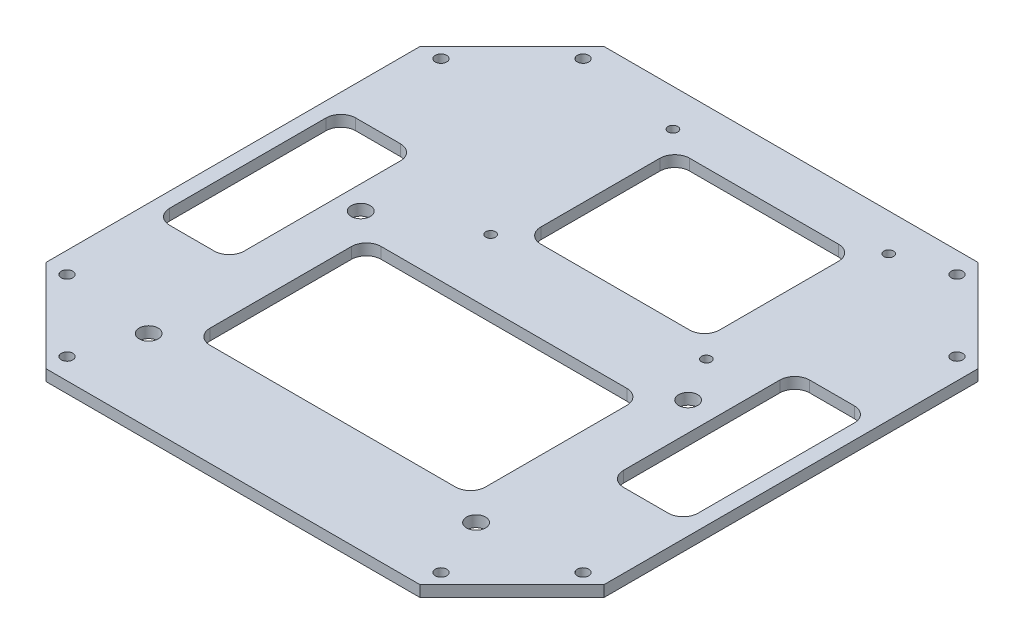
SolidWorks part; units mm, degrees
ref_plane "Front Plane" through (0, 0, 0) normal (0, 0, 1) x (1, 0, 0)
ref_plane "Top Plane" through (0, 0, 0) normal (0, 1, 0) x (1, 0, 0)
ref_plane "Right Plane" through (0, 0, 0) normal (1, 0, 0) x (0, 0, -1)
sketch "Sketch1" plane through (0, 0, 0) normal (0, 1, 0) x (1, 0, 0)
  line L1 (-75, 75) -> (75, 75)
  line L2 (-75, 75) -> (-75, -75)
  line L3 (-75, -75) -> (75, -75)
  line L4 (75, 75) -> (75, -75)
  line L5 (-75, 75) -> (75, -75) construction
  line L6 (-75, -75) -> (75, 75) construction
  point P0 (0, 0)
  dimension "D1" = 150
extrude "Boss-Extrude1" add sketch "Sketch1" along normal mid plane 3
sketch "Sketch2" plane through (0, 1.5, 0) normal (0, 1, 0) x (1, 0, 0)
  line L0 (50.2513, 75) -> (75, 75)
  line L1 (-15, 15) -> (15, 15)
  line L2 (-15, 15) -> (-15, -15)
  line L3 (-15, -15) -> (15, -15)
  line L4 (15, 15) -> (15, -15)
  line L5 (-15, 15) -> (15, -15) construction
  line L6 (-15, -15) -> (15, 15) construction
  line L7 (75, 75) -> (-75, 75) construction
  line L8 (75, -75) -> (75, 75) construction
  line L9 (75, 75) -> (75, 50.2513)
  line L10 (75, 50.2513) -> (50.2513, 75)
  line L11 (0, 0) -> (-24.6603, 0) construction
  line L12 (0, 0) -> (0, -37.7235) construction
  line L13 (-75, 75) -> (-75, 50.2513)
  line L14 (-50.2513, 75) -> (-75, 75)
  line L15 (-75, 50.2513) -> (-50.2513, 75)
  line L16 (-50.2513, -75) -> (-75, -75)
  line L17 (-75, -50.2513) -> (-50.2513, -75)
  line L18 (-75, -75) -> (-75, -50.2513)
  line L19 (75, -75) -> (75, -50.2513)
  line L20 (50.2513, -75) -> (75, -75)
  line L21 (75, -50.2513) -> (50.2513, -75)
  point P0 (0, 0)
  dimension "D1" = 30
  dimension "D2" = 35
extrude "Cut-Extrude1" cut sketch "Sketch2" against normal up to surface (3 mm away) contours L10 L0 L9 | L13 L15 L14 | L19 L21 L20 | L16 L18 L17 up to face at (0, -1.5, 0)
sketch "Sketch3" plane through (0, 1.5, 0) normal (0, 1, 0) x (1, 0, 0)
  line L0 (75, 50.2513) -> (50.2513, 75) construction
  line L1 (10, 10) -> (-10, 10)
  line L2 (10, 10) -> (10, -10)
  line L3 (10, -10) -> (-10, -10)
  line L4 (-10, 10) -> (-10, -10)
  line L5 (10, 10) -> (-10, -10) construction
  line L6 (10, -10) -> (-10, 10) construction
  line L7 (0, 0) -> (0, -7.7356) construction
  line L8 (0, 0) -> (-6.2026, 0) construction
  circle A2 centre (69.3431, 50.2513) radius 1.55
  circle A6 centre (50.2513, 69.3431) radius 1.55
  circle A7 centre (-69.3431, 50.2513) radius 1.55
  circle A12 centre (-50.2513, 69.3431) radius 1.55
  circle A14 centre (-69.3431, -50.2513) radius 1.55
  circle A18 centre (-50.2513, -69.3431) radius 1.55
  circle A19 centre (69.3431, -50.2513) radius 1.55
  circle A24 centre (50.2513, -69.3431) radius 1.55
  point P0 (0, 0)
  dimension "D2" = 13.5
  dimension "D4" = 3.1
  dimension "D8" = 4
  dimension "D1" = 20
extrude "Cut-Extrude2" cut sketch "Sketch3" against normal up to surface (3 mm away) contours A12 | A7 | A14 | A18 | A19 | A24 | A2 | A6 region at (69.3431, 1.5, -50.2513) region at (50.2513, 1.5, -69.3431) region at (-69.3431, 1.5, -50.2513) region at (-50.2513, 1.5, -69.3431) region at (-69.3431, 1.5, 50.2513) region at (-50.2513, 1.5, 69.3431) region at (69.3431, 1.5, 50.2513) region at (50.2513, 1.5, 69.3431) up to face at (0, -1.5, 0)
sketch "Sketch6" plane through (0, 1.5, 0) normal (0, 1, 0) x (1, 0, 0)
  line L0 (0, 0) -> (-24.3812, 0) construction
  line L2 (50.2513, 75) -> (-50.2513, 75) construction
  line L3 (-50.2513, -75) -> (50.2513, -75) construction
  circle A0 centre (36.2513, 16) radius 1.3
  circle A1 centre (-21.7487, 16) radius 1.3
  circle A2 centre (36.2513, 65) radius 1.3
  circle A5 centre (-21.7487, 65) radius 1.3
  circle A6 centre (-44.6569, 4) radius 2.55
  circle A10 centre (-44.6569, -53) radius 2.55
  circle A11 centre (43.3431, 4) radius 2.55
  circle A12 centre (43.3431, -53) radius 2.55
  circle A13 centre (50.2513, 69.3431) radius 1.55 construction
  circle A14 centre (69.3431, -50.2513) radius 1.55 construction
  dimension "D1" = 2.6
  dimension "D3" = 58
  dimension "D4" = 10
  dimension "D2" = 14
  dimension "D5" = 49
  dimension "D6" = 5.1
  dimension "D7" = 88
  dimension "D8" = 57
  dimension "D10" = 22
  dimension "D9" = 26
extrude "Cut-Extrude9" cut sketch "Sketch6" against normal up to surface (3 mm away) up to face at (-69.3431, -1.5, 51.8013)
sketch "Sketch7" plane through (0, 1.5, 0) normal (0, 1, 0) x (1, 0, 0)
  line L0 (75, -50.2513) -> (75, 50.2513) construction
  line L1 (71, 25) -> (51, 25)
  line L2 (71, 25) -> (71, -25)
  line L3 (71, -25) -> (51, -25)
  line L4 (51, 25) -> (51, -25)
  line L5 (71, 25) -> (51, -25) construction
  line L6 (71, -25) -> (51, 25) construction
  line L7 (0, 0) -> (-13.4247, 0) construction
  line L8 (0, 0) -> (0, -16.3557) construction
  line L14 (-71, -25) -> (-51, -25)
  line L15 (-51, 25) -> (-51, -25)
  line L16 (-71, 25) -> (-51, 25)
  line L17 (-71, 25) -> (-71, -25)
  line L19 (-16.7487, 60.5) -> (31.2513, 60.5)
  line L20 (-16.7487, 60.5) -> (-16.7487, 20.5)
  line L21 (-16.7487, 20.5) -> (31.2513, 20.5)
  line L22 (31.2513, 60.5) -> (31.2513, 20.5)
  line L23 (-16.7487, 60.5) -> (31.2513, 20.5) construction
  line L24 (-16.7487, 20.5) -> (31.2513, 60.5) construction
  line L25 (-37.6569, -1.5) -> (36.3431, -1.5)
  line L26 (-37.6569, -1.5) -> (-37.6569, -47.5)
  line L27 (-37.6569, -47.5) -> (36.3431, -47.5)
  line L28 (36.3431, -1.5) -> (36.3431, -47.5)
  line L29 (-37.6569, -1.5) -> (36.3431, -47.5) construction
  line L30 (-37.6569, -47.5) -> (36.3431, -1.5) construction
  circle A1 centre (36.2513, 65) radius 1.3 construction
  circle A2 centre (-21.7487, 65) radius 1.3 construction
  circle A3 centre (-44.6569, 4) radius 2.55 construction
  point P1 (0, 61.911)
  point P3 (61, 0)
  point P17 (7.2513, 40.5)
  point P25 (-0.6569, -24.5)
  dimension "D1" = 29
  dimension "D5" = 24.5
  dimension "D8" = 28.5
  dimension "D9" = 44
  dimension "D2" = 4
  dimension "D3" = 20
  dimension "D4" = 50
  dimension "D6" = 40
  dimension "D7" = 48
  dimension "D10" = 46
  dimension "D11" = 74
extrude "Cut-Extrude10" cut sketch "Sketch7" against normal up to surface (3 mm away) up to face at (-21.7487, -1.5, -14.7)
fillet "Fillet1" radius 4 16 edges at (71, 0, -25) (36.3431, 0, 1.5) (31.2513, 0, -60.5) (-51, 0, -25) (-51, 0, 25) (36.3431, 0, 47.5) (71, 0, 25) (31.2513, 0, -20.5) (51, 0, 25) (-37.6569, 0, 47.5) (-71, 0, 25) (-16.7487, 0, -20.5) (51, 0, -25) (-37.6569, 0, 1.5) (-71, 0, -25) (-16.7487, 0, -60.5)
